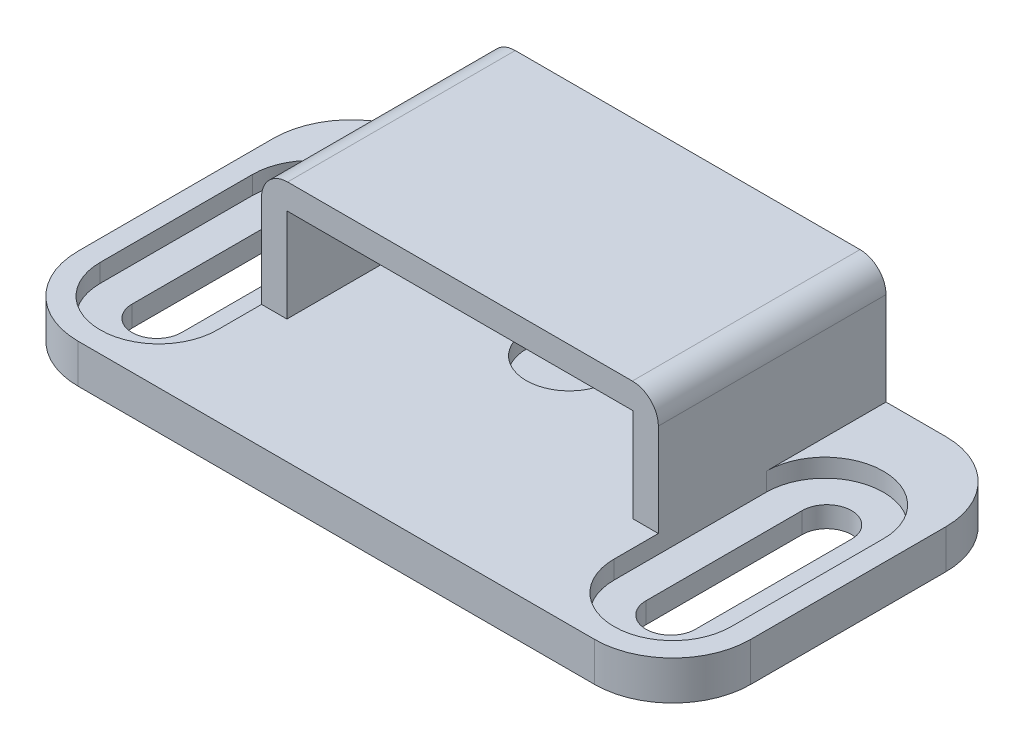
SolidWorks part; units mm, degrees
ref_plane "Front Plane" through (0, 0, 0) normal (0, 0, 1) x (1, 0, 0)
ref_plane "Top Plane" through (0, 0, 0) normal (0, 1, 0) x (1, 0, 0)
ref_plane "Right Plane" through (0, 0, 0) normal (1, 0, 0) x (0, 0, -1)
sketch "Sketch1" plane through (0, 0, 0) normal (0, 1, 0) x (1, 0, 0)
  line L1 (-19.85, -13.5) -> (19.85, -13.5)
  line L2 (-25.85, -7.5) -> (-25.85, 7.5)
  line L3 (-19.85, 13.5) -> (19.85, 13.5)
  line L4 (25.85, -7.5) -> (25.85, 7.5)
  line L5 (-25.85, -13.5) -> (25.85, 13.5) construction
  line L6 (-25.85, 13.5) -> (25.85, -13.5) construction
  arc A0 (-19.85, -13.5) -> (-25.85, -7.5) centre (-19.85, -7.5) cw
  arc A1 (19.85, -13.5) -> (25.85, -7.5) centre (19.85, -7.5) ccw
  arc A2 (19.85, 13.5) -> (25.85, 7.5) centre (19.85, 7.5) cw
  arc A3 (-25.85, 7.5) -> (-19.85, 13.5) centre (-19.85, 7.5) cw
  point P0 (0, 0)
  dimension "D3" = 6
  dimension "D1" = 51.7
  dimension "D2" = 27
extrude "Boss-Extrude1" add sketch "Sketch1" along normal blind 3
sketch "Sketch2" plane through (0, 3, 0) normal (0, 1, 0) x (1, 0, 0)
  line L0 (0, 0) -> (0, 18.8893) construction
  line L1 (0, 0) -> (0, -18.9257) construction
  line L2 (-24.25, 18.5614) -> (-24.25, -21.3666) construction
  line L3 (-25.85, 7.5) -> (-25.85, -7.5) construction
  line L4 (-15.25, 18.5614) -> (-15.25, -21.3666) construction
  line L5 (-24.25, 4.3) -> (-24.25, -7.4)
  line L6 (-15.25, 4.3) -> (-15.25, -7.4)
  line L8 (-19.85, -13.5) -> (19.85, -13.5) construction
  line L9 (24.25, 4.3) -> (24.25, -7.4)
  line L10 (15.25, 4.3) -> (15.25, -7.4)
  arc A0 (-24.25, 4.3) -> (-15.25, 4.3) centre (-19.75, 4.3) cw
  arc A1 (-24.25, -7.4) -> (-15.25, -7.4) centre (-19.75, -7.4) ccw
  arc A2 (24.25, 4.3) -> (15.25, 4.3) centre (19.75, 4.3) ccw
  arc A3 (24.25, -7.4) -> (15.25, -7.4) centre (19.75, -7.4) cw
  point P16 (-15.25, 8.1522)
  point P17 (-19.75, -11.9)
  dimension "D3" = 1.6
  dimension "D4" = 20.7
  dimension "D1" = 1.6
  dimension "D2" = 9
extrude "Cut-Extrude1" cut sketch "Sketch2" against normal blind 1.4
sketch "Sketch4" plane through (0, 3, 0) normal (0, 1, 0) x (1, 0, 0)
  line L0 (-19.75, 8.8) -> (-19.75, -20.2008) construction
  line L1 (-19.75, 8.8) -> (-19.75, 19.8729) construction
  line L2 (0, 0) -> (0, 19.4358) construction
  line L3 (0, 0) -> (0, -21.2209) construction
  line L4 (-17.85, 4.45) -> (-17.85, -7.55)
  line L5 (-21.65, 4.45) -> (-21.65, -7.55)
  line L6 (-24.25, -1.55) -> (-15.25, -1.55) construction
  line L7 (-24.25, 4.3) -> (-24.25, -7.4) construction
  line L8 (-15.25, -7.4) -> (-15.25, 4.3) construction
  line L9 (17.85, 4.45) -> (17.85, -7.55)
  line L10 (21.65, 4.45) -> (21.65, -7.55)
  arc A0 (-15.25, 4.3) -> (-24.25, 4.3) centre (-19.75, 4.3) ccw construction
  arc A1 (-17.85, 4.45) -> (-21.65, 4.45) centre (-19.75, 4.45) ccw
  arc A2 (-21.65, -7.55) -> (-17.85, -7.55) centre (-19.75, -7.55) ccw
  arc A3 (17.85, 4.45) -> (21.65, 4.45) centre (19.75, 4.45) cw
  arc A4 (21.65, -7.55) -> (17.85, -7.55) centre (19.75, -7.55) cw
  point P19 (-19.75, 6.35)
  point P20 (-21.65, -1.55)
  dimension "D1" = 3.8
  dimension "D2" = 15.8
extrude "Cut-Extrude2" cut sketch "Sketch4" against normal up to surface (3 mm away) up to face at (0, 0, 0)
sketch "Sketch5" plane through (0, 0, -13.5) normal (0, 0, -1) x (-1, 0, 0)
  line L0 (-19.85, 3) -> (19.85, 3) construction
  line L2 (-13.3, 3) -> (-13.3, 10.2)
  line L3 (-13.3, 10.2) -> (13.3, 10.2)
  line L4 (13.3, 3) -> (13.3, 10.2)
  line L5 (0, 0) -> (0, 22.1891) construction
  line L6 (15.25, 3) -> (15.25, 12.15)
  line L7 (15.25, 12.15) -> (-15.25, 12.15)
  line L8 (-15.25, 12.15) -> (-15.25, 3)
  line L9 (-15.25, 3) -> (-13.3, 3)
  line L10 (13.3, 3) -> (15.25, 3)
  point P6 (0, 0)
  point P16 (0, 0)
  dimension "D1" = 26.6
  dimension "D2" = 7.2
  dimension "D3" = 1.95
extrude "Boss-Extrude2" add sketch "Sketch5" against normal blind 17.5
fillet "Fillet1" radius 2 2 edges at (15.25, 12.15, -4.75) (-15.25, 12.15, -4.75)
sketch "Sketch8" plane through (0, 3, 0) normal (0, 1, 0) x (1, 0, 0)
  line L0 (-9.5084, 7.7) -> (9.5084, 7.7) construction
  line L1 (0, 0) -> (0, 13.5) construction
  line L2 (-13.25, 13.5) -> (13.25, 13.5) construction
  circle A0 centre (0, 4.4) radius 3.3
  dimension "D2" = 6.6
  dimension "D1" = 5.8
extrude "Cut-Extrude3" cut sketch "Sketch8" against normal blind 1.2
sketch "Sketch9" plane through (0, 10.2, 0) normal (0, -1, 0) x (1, 0, 0)
  line L0 (-11.9857, -13.5) -> (9.5448, -13.5) construction
  line L1 (19.85, -13.5) -> (-19.85, -13.5) construction
  line L2 (0, 0) -> (0, -18.0538) construction
  line L3 (-11.9857, -7.7) -> (9.5448, -7.7) construction
  circle A0 centre (0, -4.4) radius 3.3
  point P11 (9.5448, -7.7)
  point P12 (9.5448, -13.5)
  dimension "D2" = 6.6
  dimension "D1" = 5.8
extrude "Cut-Extrude4" cut sketch "Sketch9" against normal blind 1.2
ref_point "Point1"
ref_plane "Plane1" through (0, 0, -4.4) normal (0, 0, 1) x (1, 0, 0)
sketch "Sketch11" plane through (0, 0, -13.5) normal (0, 0, -1) x (-1, 0, 0)
  line L0 (0, 3) -> (3.2271, 3) construction
  line L1 (-3.3, 3) -> (3.3, 3)
  line L2 (-3.3, 3) -> (-3.3, 1.4)
  line L3 (-3.3, 1.4) -> (3.3, 1.4)
  line L4 (3.3, 3) -> (3.3, 1.4)
  line L5 (-17.696, 6.6) -> (18.1361, 6.6) construction
  line L6 (13.3, 10.2) -> (13.3, 3) construction
  line L7 (-3.3, 11.8) -> (3.3, 11.8)
  line L8 (3.3, 10.2) -> (3.3, 11.8)
  line L9 (-3.3, 10.2) -> (3.3, 10.2)
  line L10 (-3.3, 10.2) -> (-3.3, 11.8)
  point P6 (0, 1.4)
  point P14 (13.3, 6.6)
  dimension "D1" = 1.6
  dimension "D2" = 6.6
sketch "Sketch12" plane through (0, 0, -4.4) normal (0, 0, 1) x (1, 0, 0)
  line L0 (-3.3, 10.2) -> (3.3, 10.2)
  line L1 (-3.3, 3) -> (3.3, 3)
  line L2 (-3.3, 10.2) -> (-3.3, 10.4)
  line L3 (-3.3, 10.2) -> (-3.3, 11.8) construction
  line L4 (-3.3, 10.4) -> (3.3, 10.4)
  line L5 (3.3, 10.2) -> (3.3, 11.8) construction
  line L6 (3.3, 10.4) -> (3.3, 10.2)
  line L7 (-18.1361, 6.6) -> (17.696, 6.6) construction
  line L8 (-3.3, 3) -> (-3.3, 2.8)
  line L9 (-3.3, 2.8) -> (3.3, 2.8)
  line L10 (3.3, 2.8) -> (3.3, 3)
  dimension "D1" = 0.2
loft "Cut-Loft4" cut section "Sketch11" section "Sketch12"
loft "Cut-Loft7" cut section "Sketch11<110>" section "Sketch12<5>"
sketch "Sketch11<110>" plane through (0, 0, -13.5) normal (0, 0, -1) x (-1, 0, 0) same geometry as "Sketch11"
sketch "Sketch12<5>" plane through (0, 0, -4.4) normal (0, 0, 1) x (1, 0, 0) same geometry as "Sketch12"
